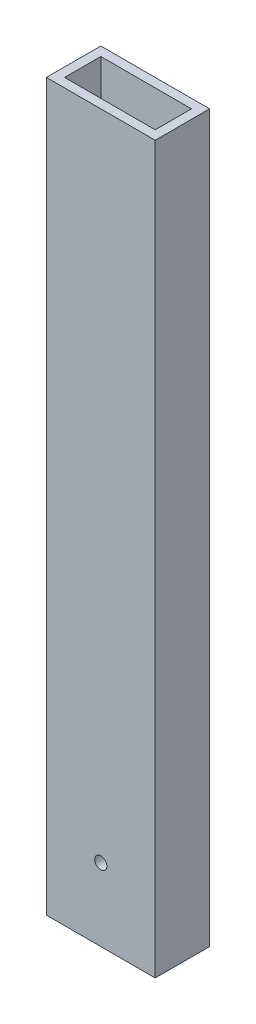
SolidWorks part; units mm, degrees
ref_plane "Front Plane" through (0, 0, 0) normal (0, 0, 1) x (1, 0, 0)
ref_plane "Top Plane" through (0, 0, 0) normal (0, 1, 0) x (1, 0, 0)
ref_plane "Right Plane" through (0, 0, 0) normal (1, 0, 0) x (0, 0, -1)
sketch "Sketch1" plane through (0, 0, 0) normal (0, 1, 0) x (1, 0, 0)
  line L0 (3.175, 15.875) -> (34.925, 15.875)
  line L1 (0, 0) -> (38.1, 0)
  line L2 (0, 0) -> (0, 19.05)
  line L3 (0, 19.05) -> (38.1, 19.05)
  line L4 (38.1, 0) -> (38.1, 19.05)
  line L5 (34.925, 3.175) -> (34.925, 15.875)
  line L6 (3.175, 3.175) -> (34.925, 3.175)
  line L7 (3.175, 3.175) -> (3.175, 15.875)
  dimension "D1" = 38.1
  dimension "D2" = 19.05
extrude "Boss-Extrude1" add sketch "Sketch1" along normal blind 254
sketch "Sketch2" plane through (0, 0, -19.05) normal (0, 0, -1) x (-1, 0, 0)
  line L0 (-38.1, 254) -> (-38.1, 0) construction
  line L1 (-38.1, 0) -> (0, 0) construction
  circle A1 centre (-19.05, 25.4) radius 2.125
  dimension "D1" = 19.05
  dimension "D2" = 25.4
extrude "Cut-Extrude1" cut sketch "Sketch2" against normal through all
